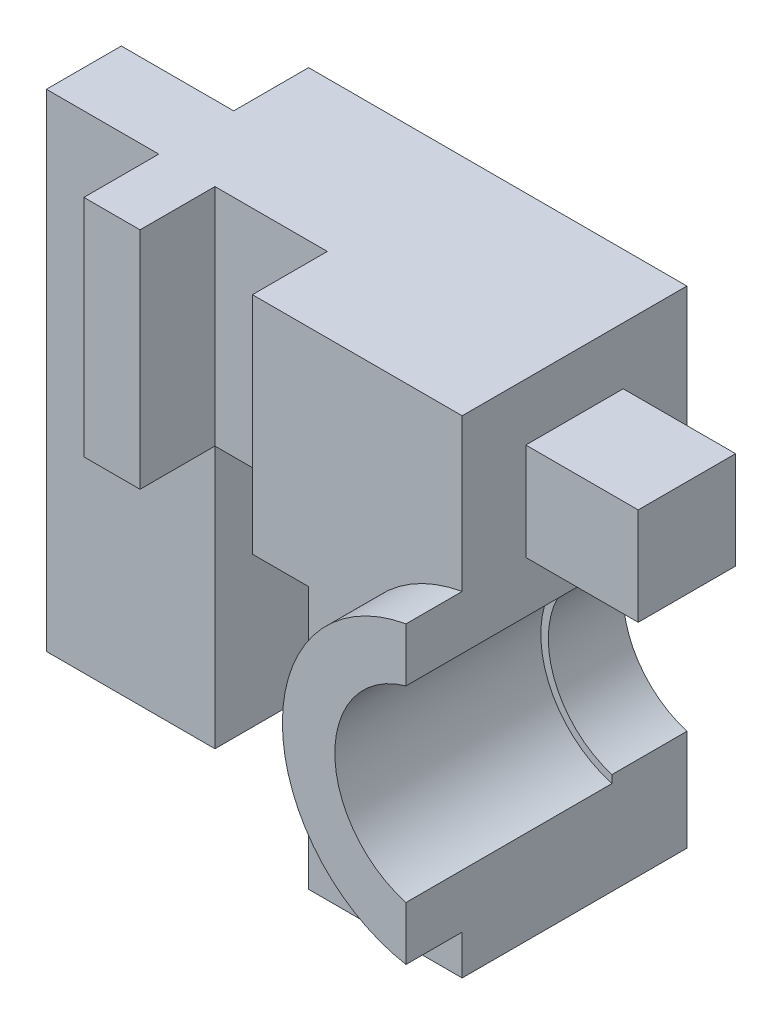
SolidWorks part; units mm, degrees
note: The reader was unsure of these and kept them because the rebuilt part matched: shared geometry of "Sketch16<3>", "Sketch16<4>".
ref_plane "Front Plane" through (0, 0, 0) normal (0, 0, 1) x (1, 0, 0)
ref_plane "Top Plane" through (0, 0, 0) normal (0, 1, 0) x (1, 0, 0)
ref_plane "Right Plane" through (0, 0, 0) normal (1, 0, 0) x (0, 0, -1)
sketch "Sketch1" plane through (0, 0, 0) normal (0, 0, 1) x (1, 0, 0)
  line L0 (-11.5, 0) -> (11.5, 0) construction
  line L1 (3.75, -5) -> (14.7, -5)
  line L2 (-14.7, -5) -> (-3.75, -5)
  line L3 (-14.7, -5) -> (-14.7, 8)
  line L4 (-14.7, 8) -> (14.7, 8)
  line L5 (14.7, -5) -> (14.7, 8)
  line L6 (-17.6832, -10.5909) -> (24.7009, -10.5909)
  line L7 (-24.9768, -7) -> (25.0232, -7) construction
  line L8 (-24.9768, -7) -> (-24.9768, -5) construction
  line L9 (-24.9768, -5) -> (-3.75, -5) construction
  line L10 (25.0232, -7) -> (25.0232, -5) construction
  line L11 (-24.9768, -7) -> (25.0232, -5) construction
  line L12 (-24.9768, -5) -> (25.0232, -7) construction
  line L13 (-5.1, -3.6128) -> (-5.1, 3.6128)
  line L14 (9, -3) -> (14, -3) construction
  line L15 (9, -3) -> (9, 3) construction
  line L16 (9, 3) -> (14, 3) construction
  line L17 (14, -3) -> (14, 3) construction
  line L18 (9, -3) -> (14, 3) construction
  line L19 (9, 3) -> (14, -3) construction
  line L20 (5.1, -3.6128) -> (5.1, 3.6128)
  line L21 (-5.1, -3.6128) -> (5.1, 3.6128) construction
  line L22 (-5.1, 3.6128) -> (5.1, -3.6128) construction
  line L23 (3.75, -5) -> (25.0232, -5) construction
  circle A0 centre (0, 0) radius 2 construction
  circle A1 centre (11.5, 0) radius 9.5 construction
  circle A2 centre (-11.5, 0) radius 9.5 construction
  circle A3 centre (11.5, 0) radius 10.5909 construction
  circle A4 centre (-11.5, 0) radius 10.5909 construction
  circle A5 centre (0, 0) radius 0.5
  circle A6 centre (-11.5, 0) radius 1
  circle A7 centre (11.5, 0) radius 1
  arc A8 (5.1, 3.6128) -> (-5.1, 3.6128) centre (0, 0) ccw
  arc A9 (-5.1, -3.6128) -> (-3.75, -5) centre (0, 0) ccw
  arc A10 (3.75, -5) -> (5.1, -3.6128) centre (0, 0) ccw
  point P13 (0, 0)
  point P17 (0, 8)
  point P18 (0.0232, -6)
  point P29 (3.5089, -10.5909)
  dimension "D1" = 4
  dimension "D2" = 19
  dimension "D5" = 1
  dimension "D6" = 2
  dimension "D9" = 12.5
  dimension "D3" = 13
  dimension "D4" = 2
  dimension "D7" = 5
  dimension "D8" = 6
  dimension "D10" = 10.2
  dimension "D11" = 8
  dimension "D12" = 3.2
extrude "Boss-Extrude1" add sketch "Sketch1" along normal blind 6 contours A10 L1 L5 L4 L3 L2 A9 L13 A8 L20 A7 A6
sketch "Sketch2" plane through (0, 0, 0) normal (0, 0, 1) x (1, 0, 0)
  circle A0 centre (-11.5, 0) radius 2.6
  circle A1 centre (11.5, 0) radius 2.6
  dimension "D1" = 5.2
extrude "Cut-Extrude1" cut sketch "Sketch2" along normal blind 6
sketch "Sketch3" plane through (0, 0, 0) normal (0, 0, 1) x (1, 0, 0)
  line L0 (-14.7, -5) -> (-3.75, -5) construction
  line L1 (-14.7, 8) -> (-22.3, 8)
  line L2 (-14.7, 8) -> (-14.7, -5)
  line L3 (-14.7, -5) -> (-22.3, -5)
  line L4 (-22.3, 8) -> (-22.3, -5)
  dimension "D1" = 7.6
extrude "Boss-Extrude2" add sketch "Sketch3" along normal blind 6
sketch "Sketch6" plane through (0, 0, 0) normal (0, 1, 0) x (1, 0, 0)
  line L0 (-22.3, -6) -> (-22.3, 0) construction
  line L1 (-22.3, -2) -> (-25.3, -2)
  line L2 (-22.3, -2) -> (-22.3, -4)
  line L3 (-22.3, -4) -> (-25.3, -4)
  line L4 (-25.3, -2) -> (-25.3, -4)
  line L5 (14.7, -6) -> (14.7, 0) construction
  line L6 (14.7, -2) -> (17.7, -2)
  line L7 (14.7, -2) -> (14.7, -4)
  line L8 (14.7, -4) -> (17.7, -4)
  line L9 (17.7, -2) -> (17.7, -4)
  point P12 (-22.3, -3)
  point P13 (-22.3, -3)
  dimension "D1" = 2
  dimension "D2" = 3
extrude "Boss-Extrude5" add sketch "Sketch6" along normal up to surface (13 mm away) from surface
sketch "Sketch10" plane through (0, 0, 6) normal (0, 0, 1) x (1, 0, 0)
  line L0 (14.7, 2.4) -> (14.7, -2.4)
  line L2 (14.7, -5) -> (14.7, 8) construction
  circle A0 centre (-11.5, 0) radius 2.6
  circle A1 centre (11.5, 0) radius 2.6
  circle A2 centre (-11.5, 0) radius 2.6 construction
  circle A3 centre (11.5, 0) radius 2.6 construction
  arc A4 (14.7, 2.4) -> (14.7, -2.4) centre (11.5, 0) ccw
  circle A5 centre (-11.5, 0) radius 4
  dimension "D1" = 8
extrude "Boss-Extrude6" add sketch "Sketch10" along normal blind 1.5
sketch "Sketch12" plane through (0, 0, 0) normal (0, 0, -1) x (-1, 0, 0)
  circle A0 centre (-11.5, 0) radius 2.4
  circle A1 centre (11.5, 0) radius 2.4
  circle A2 centre (11.5, 0) radius 2.6
  circle A3 centre (-11.5, 0) radius 2.6
  circle A4 centre (-11.5, 0) radius 2.6 construction
  circle A5 centre (11.5, 0) radius 2.6 construction
  dimension "D1" = 4.8
extrude "Boss-Extrude7" add sketch "Sketch12" against normal blind 2
sketch "Sketch13" plane through (0, -5, 0) normal (0, -1, 0) x (1, 0, 0)
  line L10 (-22.3, 6) -> (-16.3, 6)
  line L11 (-22.3, 6) -> (-3.75, 6) construction
  line L12 (-16.3, 6) -> (-16.3, 4)
  line L13 (-16.3, 4) -> (-17.8, 4)
  line L14 (-17.8, 4) -> (-17.8, 0)
  line L15 (-22.3, 0) -> (-3.75, 0) construction
  line L16 (-17.8, 0) -> (-20.8, 0)
  line L17 (-20.8, 0) -> (-20.8, 4)
  line L18 (-20.8, 4) -> (-22.3, 4)
  line L19 (-22.3, 6) -> (-22.3, 4) construction
  line L20 (-22.3, 4) -> (-22.3, 6)
  dimension "D1" = 2
  dimension "D2" = 6
  dimension "D3" = 3
extrude "Cut-Extrude2" cut sketch "Sketch13" against normal blind 7
sketch "Sketch14" plane through (0, 2, 0) normal (0, -1, 0) x (1, 0, 0)
  line L0 (-16.3, 6) -> (-22.3, 6) construction
  line L1 (-20.8, 4) -> (-17.8, 4)
  line L2 (-20.8, 4) -> (-20.8, 6)
  line L3 (-20.8, 6) -> (-17.8, 6)
  line L4 (-17.8, 4) -> (-17.8, 6)
  line L5 (-17.8, 0) -> (-17.8, 4) construction
extrude "Cut-Extrude3" cut sketch "Sketch14" against normal blind 7
sketch "Sketch15" plane through (0, 0, 0) normal (0, 0, 1) x (1, 0, 0)
  line L0 (-17.8, 8) -> (14.7, 8) construction
  line L1 (-12.2, -5) -> (-12, -5)
  line L2 (-12.2, -5) -> (-12.2, 8)
  line L3 (-12.2, 8) -> (-12, 8)
  line L4 (-12, -5) -> (-12, 8)
  line L5 (-12.2, -5) -> (-12, 8) construction
  line L6 (-12.2, 8) -> (-12, -5) construction
  line L7 (0, 0) -> (0, 6.25) construction
  line L8 (-16.3, -5) -> (-3.75, -5) construction
  line L9 (12.2, 8) -> (12, 8)
  line L10 (12, -5) -> (12, 8)
  line L11 (12.2, -5) -> (12, -5)
  line L12 (12.2, -5) -> (12.2, 8)
  arc A0 (5.1, 3.6128) -> (-5.1, 3.6128) centre (0, 0) ccw construction
  point P0 (-12.1, 1.5)
  dimension "D1" = 0.2
  dimension "D2" = 24
extrude "Cut-Extrude4" cut sketch "Sketch15" against normal mid plane 19
sketch "Sketch16" plane through (-12, 0, 0) normal (-1, 0, 0) x (0, 0, 1)
  line L0 (6, 8) -> (0, 2.3473) construction
  line L1 (4.3, 6.4737) -> (1.7, 6.4737)
  line L2 (4.5, 3.6737) -> (1.5, 3.6737)
  line L3 (4.5, 3.6737) -> (4.5, 6.6737)
  line L4 (4.5, 6.6737) -> (1.5, 6.6737)
  line L5 (1.5, 3.6737) -> (1.5, 6.6737)
  line L6 (4.5, 3.6737) -> (1.5, 6.6737) construction
  line L7 (4.5, 6.6737) -> (1.5, 3.6737) construction
  line L8 (1.7, 3.8737) -> (1.7, 6.4737)
  line L9 (4.3, 3.8737) -> (1.7, 3.8737)
  line L10 (4.3, 3.8737) -> (4.3, 6.4737)
  point P4 (3, 5.1737)
  dimension "D1" = 3
  dimension "D2" = 0.2
extrude "Cut-Extrude5" cut sketch "Sketch16" against normal blind 3 contours L4 L5 L2 L3
mirror "Mirror1" about plane through (0, 0, 0) normal (1, 0, 0) of "Cut-Extrude5"
extrude "Boss-Extrude8" add sketch "Sketch16<3>" against normal blind 3 from surface at 0.2 contours L10 L1 L8 L9 starting at face at (-12.2, 4.1845, 3.875)
sketch "Sketch16<3>" plane through (-12, 0, 0) normal (-1, 0, 0) x (0, 0, 1) same geometry as "Sketch16"
extrude "Boss-Extrude9" add sketch "Sketch16<4>" along normal blind 3 from surface at -24.2 contours L9 L8 L1 L10 starting at face at (12.2, 4.1845, 3.875)
sketch "Sketch16<4>" plane through (-12, 0, 0) normal (-1, 0, 0) x (0, 0, 1) same geometry as "Sketch16"
sketch "Sketch17" plane through (0, 0, 0) normal (0, 0, 1) x (1, 0, 0)
  line L1 (-12, 8) -> (17.7, 8)
  line L2 (-12, 8) -> (-12, -5)
  line L3 (-12, -5) -> (17.7, -5)
  line L4 (17.7, 8) -> (17.7, -5)
extrude "Cut-Extrude6" cut sketch "Sketch17" along normal blind 10
sketch "Sketch18" plane through (-12.2, 0, 0) normal (1, 0, 0) x (0, 0, -1)
  line L1 (-4.3, 6.4737) -> (-1.7, 6.4737)
  line L2 (-4.3, 6.4737) -> (-4.3, 3.8737)
  line L3 (-4.3, 3.8737) -> (-1.7, 3.8737)
  line L4 (-1.7, 6.4737) -> (-1.7, 3.8737)
extrude "Boss-Extrude10" add sketch "Sketch18" along normal blind 3
